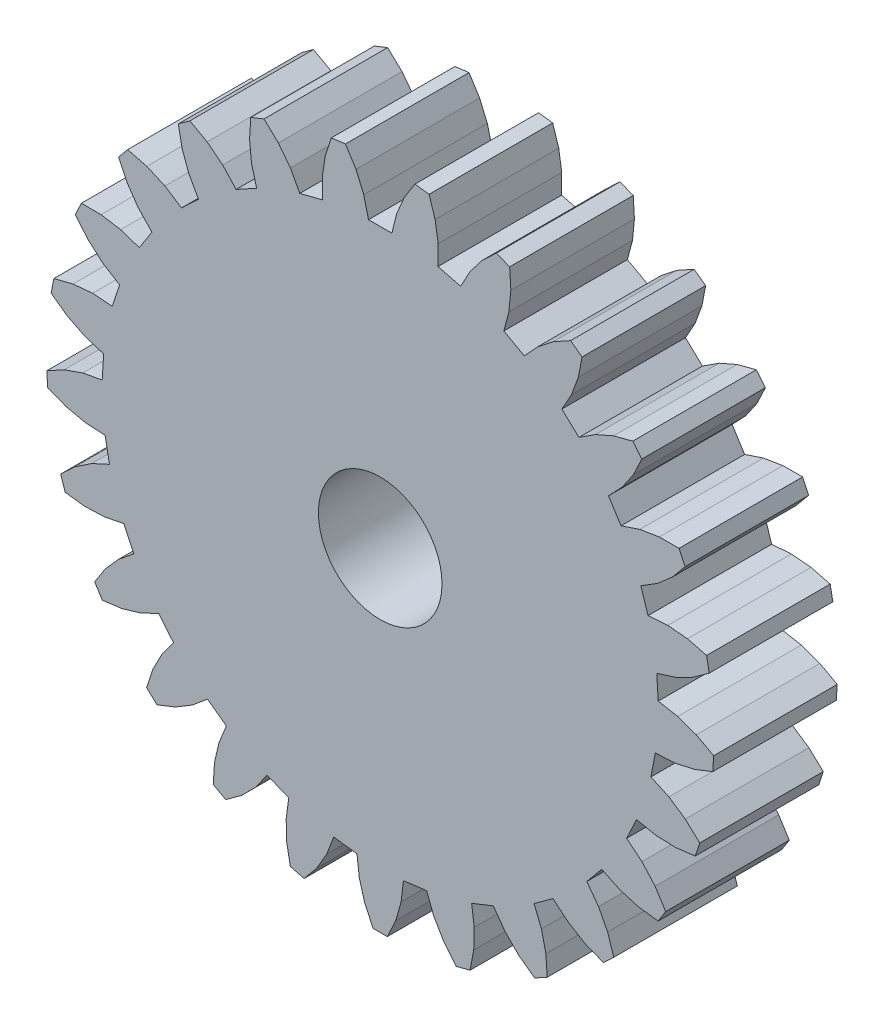
SolidWorks part; units mm, degrees
ref_plane "Front Plane" through (0, 0, 0) normal (0, 0, 1) x (1, 0, 0)
ref_plane "Top Plane" through (0, 0, 0) normal (0, 1, 0) x (1, 0, 0)
ref_plane "Right Plane" through (0, 0, 0) normal (1, 0, 0) x (0, 0, -1)
sketch "Sketch3" plane through (0, 0, 0) normal (0, 0, 1) x (1, 0, 0)
  line L0 (-2.8117, 26.9235) -> (-3.9548, 26.7791)
  line L1 (-3.9548, 26.7791) -> (-4.4453, 25.2575)
  line L2 (-4.4453, 25.2575) -> (-4.6871, 23.6772)
  line L3 (-4.6871, 23.6772) -> (-4.6739, 22.0785)
  line L5 (-0.9462, 22.5494) -> (-1.331, 24.1011)
  line L6 (-1.331, 24.1011) -> (-1.9582, 25.5717)
  line L7 (-1.9582, 25.5717) -> (-2.8117, 26.9235)
  line L8 (-9.4015, 25.3807) -> (-10.4728, 24.9565)
  line L9 (-10.4728, 24.9565) -> (-10.5694, 23.3607)
  line L10 (-10.5694, 23.3607) -> (-10.4106, 21.7699)
  line L11 (-10.4106, 21.7699) -> (-10.0003, 20.2247)
  line L13 (-6.5068, 21.6079) -> (-7.2654, 23.0152)
  line L14 (-7.2654, 23.0152) -> (-8.2386, 24.2836)
  line L15 (-8.2386, 24.2836) -> (-9.4015, 25.3807)
  line L16 (-15.4005, 22.2474) -> (-16.3327, 21.5702)
  line L17 (-16.3327, 21.5702) -> (-16.0295, 20.0005)
  line L18 (-16.0295, 20.0005) -> (-15.48, 18.4992)
  line L19 (-15.48, 18.4992) -> (-14.6983, 17.1046)
  line L21 (-11.6585, 19.3131) -> (-12.7433, 20.4875)
  line L22 (-12.7433, 20.4875) -> (-14.0013, 21.474)
  line L23 (-14.0013, 21.474) -> (-15.4005, 22.2474)
  line L24 (-16.0777, 15.8092) -> (-17.4205, 16.6769)
  line L25 (-17.4205, 16.6769) -> (-18.8844, 17.3196)
  line L26 (-18.8844, 17.3196) -> (-20.4319, 17.7207)
  line L27 (-20.4319, 17.7207) -> (-21.1663, 16.833)
  line L28 (-21.1663, 16.833) -> (-20.4823, 15.388)
  line L29 (-20.4823, 15.388) -> (-19.5767, 14.0705)
  line L30 (-19.5767, 14.0705) -> (-18.4728, 12.9141)
  line L32 (-19.4867, 11.3164) -> (-21.0031, 11.8229)
  line L33 (-21.0031, 11.8229) -> (-22.5808, 12.0813)
  line L34 (-22.5808, 12.0813) -> (-24.1795, 12.085)
  line L35 (-24.1795, 12.085) -> (-24.6701, 11.0425)
  line L36 (-24.6701, 11.0425) -> (-23.6482, 9.813)
  line L37 (-23.6482, 9.813) -> (-22.4434, 8.7621)
  line L38 (-22.4434, 8.7621) -> (-21.0865, 7.9166)
  line L40 (-21.6713, 6.1169) -> (-23.266, 6.2304)
  line L41 (-23.266, 6.2304) -> (-24.8584, 6.0884)
  line L42 (-24.8584, 6.0884) -> (-26.4078, 5.6944)
  line L43 (-26.4078, 5.6944) -> (-26.6237, 4.5626)
  line L44 (-26.6237, 4.5626) -> (-25.3281, 3.6259)
  line L45 (-25.3281, 3.6259) -> (-23.8998, 2.9076)
  line L46 (-23.8998, 2.9076) -> (-22.3754, 2.4261)
  line L48 (-22.4942, 0.5375) -> (-24.067, 0.2509)
  line L49 (-24.067, 0.2509) -> (-25.574, -0.2827)
  line L50 (-25.574, -0.2827) -> (-26.9768, -1.0497)
  line L51 (-26.9768, -1.0497) -> (-26.9044, -2.1996)
  line L52 (-26.9044, -2.1996) -> (-25.4166, -2.7847)
  line L53 (-25.4166, -2.7847) -> (-23.8546, -3.1252)
  line L54 (-23.8546, -3.1252) -> (-22.2582, -3.2124)
  line L56 (-21.9036, -5.0712) -> (-23.3558, -5.74)
  line L57 (-23.3558, -5.74) -> (-24.6828, -6.6316)
  line L58 (-24.6828, -6.6316) -> (-25.8507, -7.7233)
  line L59 (-25.8507, -7.7233) -> (-25.4947, -8.8191)
  line L60 (-25.4947, -8.8191) -> (-23.9081, -9.0158)
  line L61 (-23.9081, -9.0158) -> (-22.3104, -8.9572)
  line L62 (-22.3104, -8.9572) -> (-20.7426, -8.6447)
  line L64 (-19.9368, -10.3569) -> (-21.177, -11.3658)
  line L65 (-21.177, -11.3658) -> (-22.2406, -12.5594)
  line L66 (-22.2406, -12.5594) -> (-23.1004, -13.9073)
  line L67 (-23.1004, -13.9073) -> (-22.483, -14.8801)
  line L68 (-22.483, -14.8801) -> (-20.8973, -14.6761)
  line L69 (-20.8973, -14.6761) -> (-19.3645, -14.222)
  line L70 (-19.3645, -14.222) -> (-17.9236, -13.5294)
  line L72 (-16.7174, -14.9874) -> (-17.6677, -16.273)
  line L73 (-17.6677, -16.273) -> (-18.401, -17.6937)
  line L74 (-18.401, -17.6937) -> (-18.8985, -19.213)
  line L75 (-18.8985, -19.213) -> (-18.0586, -20.0017)
  line L76 (-18.0586, -20.0017) -> (-16.5735, -19.4098)
  line L77 (-16.5735, -19.4098) -> (-15.2017, -18.5887)
  line L78 (-15.2017, -18.5887) -> (-13.9783, -17.5595)
  line L80 (-12.4474, -18.6718) -> (-13.0482, -20.1533)
  line L81 (-13.0482, -20.1533) -> (-13.4052, -21.7117)
  line L82 (-13.4052, -21.7117) -> (-13.5092, -23.307)
  line L83 (-13.5092, -23.307) -> (-12.4996, -23.8621)
  line L84 (-12.4996, -23.8621) -> (-11.2083, -22.9194)
  line L85 (-11.2083, -22.9194) -> (-10.0838, -21.783)
  line L86 (-10.0838, -21.783) -> (-9.1548, -20.4819)
  line L88 (-7.3954, -21.1785) -> (-7.6088, -22.7629)
  line L89 (-7.6088, -22.7629) -> (-7.5671, -24.3611)
  line L90 (-7.5671, -24.3611) -> (-7.2711, -25.9322)
  line L91 (-7.2711, -25.9322) -> (-6.1551, -26.2187)
  line L92 (-6.1551, -26.2187) -> (-5.1389, -24.9846)
  line L93 (-5.1389, -24.9846) -> (-4.3324, -23.6042)
  line L94 (-4.3324, -23.6042) -> (-3.7561, -22.1129)
  line L96 (-1.8787, -22.3501) -> (-1.6914, -23.9378)
  line L97 (-1.6914, -23.9378) -> (-1.2535, -25.4754)
  line L98 (-1.2535, -25.4754) -> (-0.5761, -26.9235)
  line L99 (-0.5761, -26.9235) -> (0.5761, -26.9235)
  line L100 (0.5761, -26.9235) -> (1.2534, -25.4754)
  line L101 (1.2534, -25.4754) -> (1.6914, -23.9378)
  line L102 (1.6914, -23.9378) -> (1.8787, -22.3501)
  line L104 (3.7561, -22.1129) -> (4.3323, -23.6042)
  line L105 (4.3323, -23.6042) -> (5.1389, -24.9846)
  line L106 (5.1389, -24.9846) -> (6.1551, -26.2187)
  line L107 (6.1551, -26.2187) -> (7.2711, -25.9322)
  line L108 (7.2711, -25.9322) -> (7.567, -24.3611)
  line L109 (7.567, -24.3611) -> (7.6088, -22.7629)
  line L110 (7.6088, -22.7629) -> (7.3954, -21.1785)
  line L112 (9.1548, -20.4819) -> (10.0838, -21.783)
  line L113 (10.0838, -21.783) -> (11.2083, -22.9194)
  line L114 (11.2083, -22.9194) -> (12.4995, -23.8621)
  line L115 (12.4995, -23.8621) -> (13.5092, -23.307)
  line L116 (13.5092, -23.307) -> (13.4051, -21.7117)
  line L117 (13.4051, -21.7117) -> (13.0482, -20.1533)
  line L118 (13.0482, -20.1533) -> (12.4474, -18.6718)
  line L120 (13.9783, -17.5595) -> (15.2017, -18.5887)
  line L121 (15.2017, -18.5887) -> (16.5735, -19.4098)
  line L122 (16.5735, -19.4098) -> (18.0586, -20.0017)
  line L123 (18.0586, -20.0017) -> (18.8985, -19.213)
  line L124 (18.8985, -19.213) -> (18.401, -17.6937)
  line L125 (18.401, -17.6937) -> (17.6676, -16.273)
  line L126 (17.6676, -16.273) -> (16.7173, -14.9874)
  line L128 (17.9235, -13.5294) -> (19.3645, -14.222)
  line L129 (19.3645, -14.222) -> (20.8973, -14.6761)
  line L130 (20.8973, -14.6761) -> (22.483, -14.8801)
  line L131 (22.483, -14.8801) -> (23.1003, -13.9073)
  line L132 (23.1003, -13.9073) -> (22.2406, -12.5594)
  line L133 (22.2406, -12.5594) -> (21.177, -11.3658)
  line L134 (21.177, -11.3658) -> (19.9368, -10.3569)
  line L136 (20.7425, -8.6447) -> (22.3104, -8.9572)
  line L137 (22.3104, -8.9572) -> (23.9081, -9.0158)
  line L138 (23.9081, -9.0158) -> (25.4946, -8.8191)
  line L139 (25.4946, -8.8191) -> (25.8507, -7.7233)
  line L140 (25.8507, -7.7233) -> (24.6828, -6.6316)
  line L141 (24.6828, -6.6316) -> (23.3558, -5.74)
  line L142 (23.3558, -5.74) -> (21.9036, -5.0712)
  line L144 (22.2582, -3.2124) -> (23.8545, -3.1252)
  line L145 (23.8545, -3.1252) -> (25.4166, -2.7847)
  line L146 (25.4166, -2.7847) -> (26.9044, -2.1996)
  line L147 (26.9044, -2.1996) -> (26.9768, -1.0497)
  line L148 (26.9768, -1.0497) -> (25.574, -0.2827)
  line L149 (25.574, -0.2827) -> (24.067, 0.2509)
  line L150 (24.067, 0.2509) -> (22.4941, 0.5375)
  line L152 (22.3753, 2.4261) -> (23.8998, 2.9076)
  line L153 (23.8998, 2.9076) -> (25.3281, 3.6259)
  line L154 (25.3281, 3.6259) -> (26.6236, 4.5626)
  line L155 (26.6236, 4.5626) -> (26.4078, 5.6944)
  line L156 (26.4078, 5.6944) -> (24.8584, 6.0884)
  line L157 (24.8584, 6.0884) -> (23.2659, 6.2304)
  line L158 (23.2659, 6.2304) -> (21.6712, 6.1169)
  line L160 (21.0865, 7.9166) -> (22.4433, 8.7621)
  line L161 (22.4433, 8.7621) -> (23.6481, 9.813)
  line L162 (23.6481, 9.813) -> (24.6701, 11.0425)
  line L163 (24.6701, 11.0425) -> (24.1795, 12.085)
  line L164 (24.1795, 12.085) -> (22.5807, 12.0813)
  line L165 (22.5807, 12.0813) -> (21.003, 11.8229)
  line L166 (21.003, 11.8229) -> (19.4867, 11.3164)
  line L168 (18.4727, 12.9141) -> (19.5767, 14.0705)
  line L169 (19.5767, 14.0705) -> (20.4823, 15.388)
  line L170 (20.4823, 15.388) -> (21.1663, 16.833)
  line L171 (21.1663, 16.833) -> (20.4319, 17.7207)
  line L172 (20.4319, 17.7207) -> (18.8843, 17.3196)
  line L173 (18.8843, 17.3196) -> (17.4205, 16.6769)
  line L174 (17.4205, 16.6769) -> (16.0777, 15.8092)
  line L176 (18.4727, 12.9141) -> (19.4867, 11.3164)
  line L177 (14.6983, 17.1046) -> (15.48, 18.4992)
  line L178 (15.48, 18.4992) -> (16.0295, 20.0005)
  line L179 (16.0295, 20.0005) -> (16.3327, 21.5702)
  line L180 (16.3327, 21.5702) -> (15.4005, 22.2474)
  line L181 (15.4005, 22.2474) -> (14.0013, 21.474)
  line L182 (14.0013, 21.474) -> (12.7433, 20.4875)
  line L183 (12.7433, 20.4875) -> (11.6585, 19.3131)
  line L185 (10.0003, 20.2247) -> (10.4106, 21.7699)
  line L186 (10.4106, 21.7699) -> (10.5694, 23.3607)
  line L187 (10.5694, 23.3607) -> (10.4727, 24.9565)
  line L188 (10.4727, 24.9565) -> (9.4014, 25.3807)
  line L189 (9.4014, 25.3807) -> (8.2386, 24.2836)
  line L190 (8.2386, 24.2836) -> (7.2654, 23.0152)
  line L191 (7.2654, 23.0152) -> (6.5067, 21.6079)
  line L193 (4.6739, 22.0785) -> (4.6871, 23.6772)
  line L194 (4.6871, 23.6772) -> (4.4453, 25.2575)
  line L195 (4.4453, 25.2575) -> (3.9548, 26.7791)
  line L196 (3.9548, 26.7791) -> (2.8117, 26.9235)
  line L197 (2.8117, 26.9235) -> (1.9581, 25.5717)
  line L198 (1.9581, 25.5717) -> (1.3309, 24.1011)
  line L199 (1.3309, 24.1011) -> (0.9462, 22.5494)
  line L201 (-6.5068, 21.6079) -> (-4.6739, 22.0785)
  line L202 (-0.9462, 22.5494) -> (0.9462, 22.5494)
  line L203 (4.6739, 22.0785) -> (6.5067, 21.6079)
  line L204 (10.0003, 20.2247) -> (11.6585, 19.3131)
  line L205 (14.6983, 17.1046) -> (16.0777, 15.8092)
  line L206 (21.0865, 7.9166) -> (21.6712, 6.1169)
  line L207 (22.3753, 2.4261) -> (22.4941, 0.5375)
  line L208 (22.2582, -3.2124) -> (21.9036, -5.0712)
  line L209 (20.7425, -8.6447) -> (19.9368, -10.3569)
  line L210 (17.9235, -13.5294) -> (16.7173, -14.9874)
  line L211 (13.9783, -17.5595) -> (12.4474, -18.6718)
  line L212 (9.1548, -20.4819) -> (7.3954, -21.1785)
  line L213 (3.7561, -22.1129) -> (1.8787, -22.3501)
  line L214 (-1.8787, -22.3501) -> (-3.7561, -22.1129)
  line L215 (-7.3954, -21.1785) -> (-9.1548, -20.4819)
  line L216 (-12.4474, -18.6718) -> (-13.9783, -17.5595)
  line L217 (-16.7174, -14.9874) -> (-17.9236, -13.5294)
  line L218 (-19.9368, -10.3569) -> (-20.7426, -8.6447)
  line L219 (-21.9036, -5.0712) -> (-22.2582, -3.2124)
  line L220 (-22.4942, 0.5375) -> (-22.3754, 2.4261)
  line L221 (-21.6713, 6.1169) -> (-21.0865, 7.9166)
  line L222 (-19.4867, 11.3164) -> (-18.4728, 12.9141)
  line L223 (-16.0777, 15.8092) -> (-14.6983, 17.1046)
  line L224 (-11.6585, 19.3131) -> (-10.0003, 20.2247)
  circle A0 centre (0, 0) radius 5
extrude "Boss-Extrude1" add sketch "Sketch3" along normal blind 10
sketch "Sketch4" plane through (0, 0, 0) normal (0, 0, -1) x (-1, 0, 0)
  circle A0 centre (0, 0) radius 5
  circle A1 centre (0, 0) radius 10
extrude "Boss-Extrude2" add sketch "Sketch4" along normal blind 3
fillet "Fillet6" radius 5.5 1 edges at (-10, 0, -3)
scale "Scale1" scale about centroid uniform scaling yes scale factor 0.8
